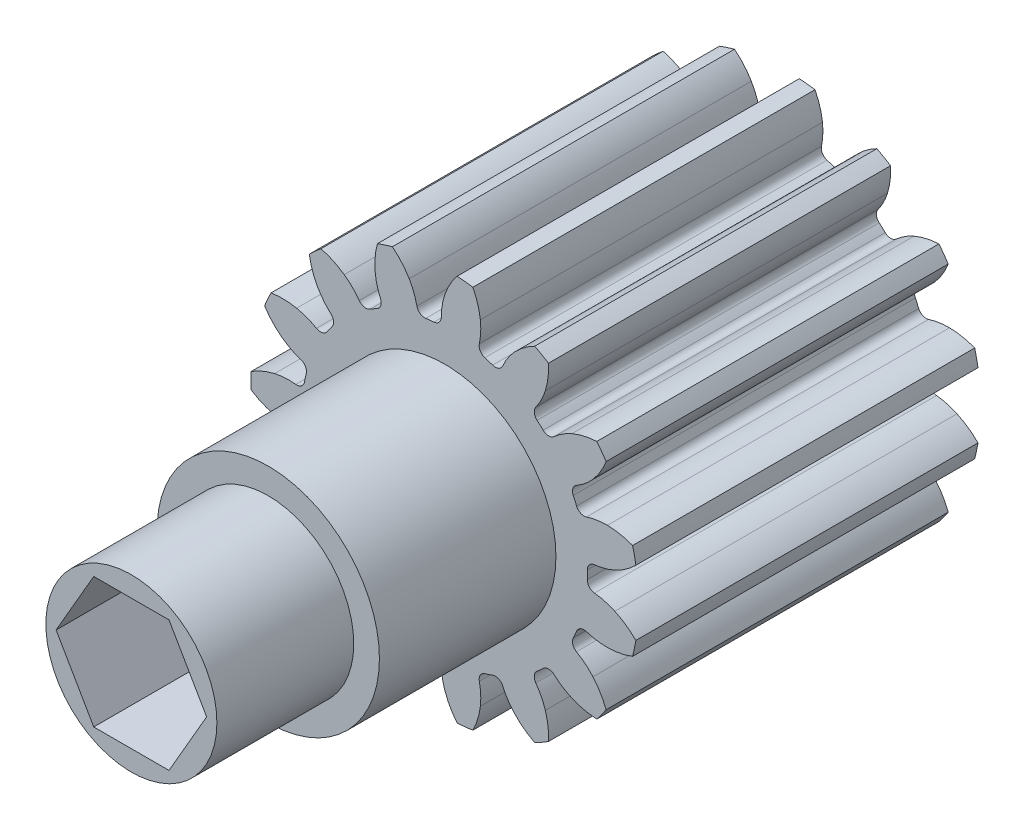
SolidWorks part; units mm, degrees
other "DetailItem7"
other "DetailItem8"
material "Markforged"
ref_plane "Front" through (0, 0, 0) normal (0, 0, 1) x (1, 0, 0)
ref_plane "Top" through (0, 0, 0) normal (0, 1, 0) x (1, 0, 0)
ref_plane "Right" through (0, 0, 0) normal (1, 0, 0) x (0, 0, -1)
sketch "Sketch1" plane through (0, 0, 0) normal (0, 0, 1) x (1, 0, 0)
  line L0 (0, 0) -> (6.35, 0) construction
  line L1 (6.35, 0) -> (7.1967, 0) construction
  circle A0 centre (0, 0) radius 6.35 construction
  circle A1 centre (0, 0) radius 7.1967
  dimension "D1" = 12.7
  dimension "D2" = 0.8467
extrude "Round Stock" add sketch "Sketch1" along normal mid plane 12.7
sketch "Sketch2" plane through (0, 0, 6.35) normal (0, 0, 1) x (1, 0, 0)
  line L0 (0, 0) -> (5.2917, 0) construction
  line L1 (5.2917, 0) -> (6.35, 0) construction
  line L2 (0, 0) -> (-7.1967, 0) construction
  line L3 (0, 0) -> (-6.5745, -2.9271) construction
  line L4 (-6.6884, -2.6565) -> (-6.0396, -1.961) construction
  line L5 (-6.0396, -1.961) -> (-5.0824, -1.4735) construction
  line L6 (-7.1907, -0.2936) -> (-6.3151, -0.6651) construction
  line L7 (-6.3151, -0.6651) -> (-5.2423, -0.7211) construction
  line L8 (-5.7691, -2.5686) -> (-6.0396, -1.961) construction
  line L9 (-6.3151, -0.6651) -> (-6.3151, 0) construction
  line L12 (0, 0) -> (-6.3151, -0.6651) construction
  line L13 (0, 0) -> (-6.0396, -1.961) construction
  line L14 (-6.0396, -1.961) -> (-4.9937, -5.1821) construction
  line L15 (-6.3151, -0.6651) -> (-6.6698, 2.703) construction
  line L16 (-6.0396, -1.961) -> (-6.3151, -0.6651) construction
  line L17 (-5.176, -1.1002) -> (-5.2423, -0.7211) construction
  line L18 (-5.176, -1.1002) -> (-5.0824, -1.4735) construction
  circle A0 centre (0, 0) radius 6.35 construction
  circle A1 centre (0, 0) radius 5.2917 construction
  circle A2 centre (0, 0) radius 7.1967 construction
  arc A3 (-6.6884, -2.6565) -> (-7.1907, -0.2936) centre (0, 0) cw
  arc A4 (-5.0824, -1.4735) -> (-5.2423, -0.7211) centre (0, 0) cw construction
  arc A6 (-6.6884, -2.6565) -> (-6.0396, -1.961) centre (-4.4502, -4.0942) cw
  arc A7 (-7.1907, -0.2936) -> (-6.3151, -0.6651) centre (-5.7307, 1.9302) ccw
  arc A8 (-6.0396, -1.961) -> (-5.3395, -1.6003) centre (-4.6032, -3.8888) cw
  arc A9 (-6.3151, -0.6651) -> (-5.5288, -0.7099) centre (-5.787, 1.6803) ccw
  arc A10 (-5.3395, -1.6003) -> (-5.1423, -1.2483) centre (-5.4303, -1.3182) ccw
  arc A11 (-5.5288, -0.7099) -> (-5.2055, -0.9512) centre (-5.497, -1.0045) cw
  arc A12 (-5.1423, -1.2483) -> (-5.2055, -0.9512) centre (0, 0) cw
  dimension "D6" = 12.7
  dimension "D9" = 0.2963
  dimension "D12" = 2.6602
  dimension "D2" = 1.0583
  dimension "D3" = 24
  dimension "D4" = 0.6651
  dimension "D5" = 0.6651
  dimension "D11" = 1.3249
  dimension "D8" = 20
  dimension "D7" = 20
  dimension "D14" = 9
  dimension "D15" = 9
extrude "Single Tooth" cut sketch "Sketch2" against normal through all
ref_axis "Axis" through (0, 0, 50) along (0, 0, -1)
pattern_circular "Tooth Pattern" count 15 over 360 about axis through (0, 0, 50) along (0, 0, -1) of "Single Tooth"
sketch "Sketch4" plane through (0, 0, 6.35) normal (0, 0, 1) x (1, 0, 0)
  circle A0 centre (0, 0) radius 3.175
  dimension "D1" = 6.35
extrude "TopBearingBoss" add sketch "Sketch4" along normal blind 11.6332
mirror "BottomBearingBoss" [suppressed] about plane through (0, 0, 0) normal (0, 0, 1)
sketch "Sketch5" plane through (0, 0, 0) normal (0, 0, 1) x (1, 0, 0)
  circle A0 centre (0, 0) radius 2.4193
  dimension "D1" = 4.8387
extrude "RoundBore" cut sketch "Sketch5" against normal through all both and the other way through all
sketch "Sketch6" plane through (0, 0, 0) normal (0, 0, 1) x (1, 0, 0)
  line L1 (1.3968, 2.4194) -> (-1.3968, 2.4193)
  line L2 (-1.3968, 2.4193) -> (-2.7936, 0)
  line L3 (-2.7936, 0) -> (-1.3968, -2.4194)
  line L4 (-1.3968, -2.4194) -> (1.3968, -2.4194)
  line L5 (1.3968, -2.4194) -> (2.7936, 0)
  line L6 (2.7936, 0) -> (1.3968, 2.4194)
  circle A0 centre (0, 0) radius 2.4193 construction
  circle A1 centre (0, 0) radius 2.4193 construction
extrude "Hex" cut sketch "Sketch6" against normal through all both and the other way through all
sketch "Sketch7" plane through (0, 0, 6.35) normal (0, 0, 1) x (1, 0, 0)
  line L0 (-10.955, 3.3496) -> (10.955, 3.3496) construction
  line L1 (0, 0) -> (0, 3.3496) construction
  text T0 "15" font "Adobe Gothic Std B" height 3.5
  dimension "D1" = 3.3496
extrude "ToothCount" [suppressed] cut sketch "Sketch7" against normal blind 0.762
sketch "Sketch8" plane through (0, 0, 6.35) normal (0, 0, 1) x (1, 0, 0)
  circle A0 centre (0, 0) radius 4.1275
  circle A1 centre (0, 0) radius 3.175 construction
  circle A2 centre (0, 0) radius 3.175
  dimension "D1" = 8.255
extrude "Boss-Extrude1" add sketch "Sketch8" along normal offset from surface (6.5532 mm away) 5.08 up to face at (0, 0, 17.9832)
sketch "Sketch9" plane through (0, 0, -6.35) normal (0, 0, -1) x (-1, 0, 0)
  line L6 (1.3968, -2.4194) -> (2.7936, 0)
  line L7 (-1.3968, -2.4194) -> (1.3968, -2.4194)
  line L8 (-2.7936, 0) -> (-1.3968, -2.4194)
  line L9 (-1.3968, 2.4194) -> (-2.7936, 0)
  line L10 (1.3968, 2.4193) -> (-1.3968, 2.4194)
  line L11 (2.7936, 0) -> (1.3968, 2.4193)
  line L12 (1.3968, -2.4194) -> (2.7936, 0)
  line L13 (-1.3968, -2.4194) -> (1.3968, -2.4194)
  line L14 (-2.7936, 0) -> (-1.3968, -2.4194)
  line L15 (-1.3968, 2.4194) -> (-2.7936, 0)
  line L16 (1.3968, 2.4193) -> (-1.3968, 2.4194)
  line L17 (2.7936, 0) -> (1.3968, 2.4193)
  circle A0 centre (0, 0) radius 1.778
  dimension "D2" = 3.556
  dimension "D1" = 0
extrude "Boss-Extrude2" add sketch "Sketch9" against normal blind 3.175
equation "\"N_teeth\"= \"No_Teeth\""
equation "\"pitch_diameter\"= \"N_teeth\" / \"Pitch\""
equation "\"Pd\"=\"N_teeth\"/\"pitch_diameter\""
equation "\"addendum\"=1.000/\"Pd\""
equation "\"face_width\"=0.5"
equation "\"deddendum\"=1.250/\"Pd\""
equation "\"D3@Sketch2\" = 360/\"N_teeth\""
equation "\"tooth_thickness\"=1.571/\"Pd\""
equation "\"D4@Sketch2\" = \"tooth_thickness\"/2"
equation "\"D5@Sketch2\" = \"tooth_thickness\"/2"
equation "\"Pressure_Angle\"= iif ( \"Pitch\" = 20 , 14.500000 , iif ( \"Pitch\" = 32 , 20 , 20 ) )"
equation "\"base_fillet\"=0.35/\"Pd\""
equation "\"D12@Sketch2\" = 2*\"tooth_thickness\""
equation "\"hub_projection\"=0.250000"
equation "\"sss_diam\"= 0.062500"
equation "\"D1@Sketch1\"=\"pitch_diameter\""
equation "\"D2@Sketch1\"=\"addendum\""
equation "\"D1@Round Stock\" = \"face_width\""
equation "\"D2@Sketch2\"=\"deddendum\""
equation "\"D6@Sketch2\"=\"pitch_diameter\""
equation "\"D7@Sketch2\"=\"Pressure_Angle\""
equation "\"D8@Sketch2\"=\"D7@Sketch2\""
equation "\"D9@Sketch2\"=\"base_fillet\""
equation "\"D1@Tooth Pattern\" = \"N_teeth\""
equation "\"Pitch\"= \"GearPitch\""
equation "\"BossDia\"= \"BoreDia\" * 1.3"
equation "\"D1@Sketch5\"=\"BoreDia\"+\"PrintTol\""
equation "\"Hex\"= iif ( \"HexBore\" = 1 , \"unsuppressed\" , \"suppressed\" )"
equation "\"TopBearingBoss\" = iif ( \"Bearing_Boss\" = 0 , \"suppressed\" , \"unsuppressed\" )"
equation "\"BottomBearingBoss\"= iif ( \"Bearing_Boss\" > 1 , \"unsuppressed\" , \"suppressed\" )"
equation "\"D1@Sketch7\"=\"BossDia\"/2+.01"
equation "\"ToothCount\"= iif ( \"No_Teeth\" < 22 , \"suppressed\" , \"unsuppressed\" )"
